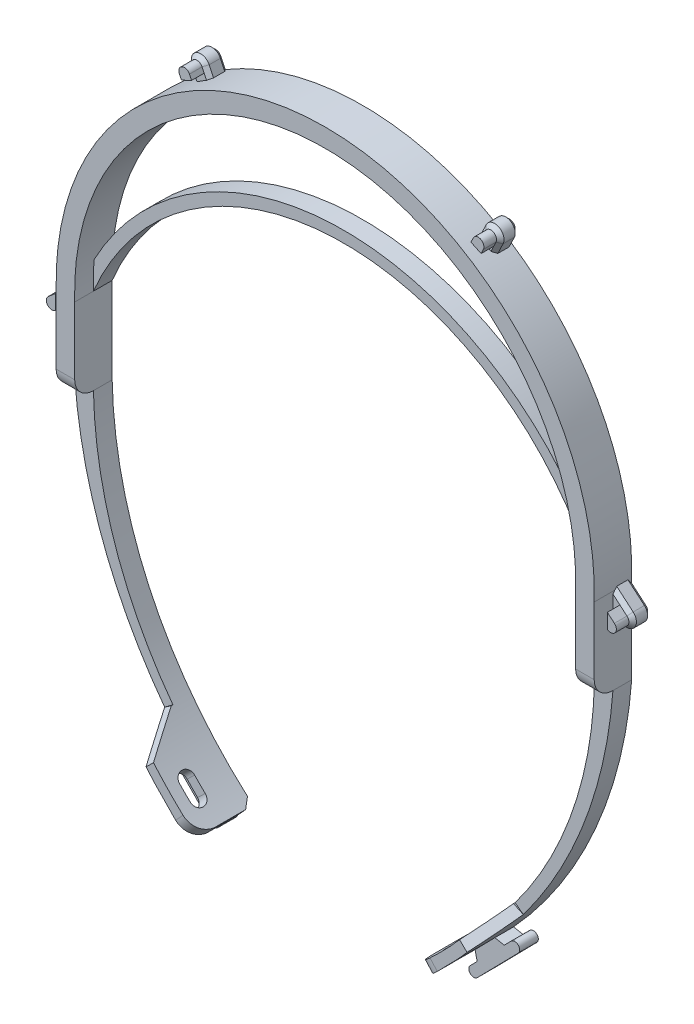
SolidWorks part; units mm, degrees
ref_plane "Plan de face" through (0, 0, 0) normal (0, 0, 1) x (1, 0, 0)
ref_plane "Plan de dessus" through (0, 0, 0) normal (0, 1, 0) x (1, 0, 0)
ref_plane "Plan de droite" through (0, 0, 0) normal (1, 0, 0) x (0, 0, -1)
sketch "Model" plane through (0, 0, 0) normal (0, 0, 1) x (1, 0, 0)
  line L0 (55.1962, 55.166) -> (59.6015, 49.7259) construction
  line L1 (19.4014, 75.8321) -> (26.163, 74.0203) construction
  line L2 (44.8062, 64.5211) -> (50.2463, 60.1158) construction
  line L3 (-41.0201, -88.1014) -> (-30.0985, -99.2461) construction
  line L4 (-41.1662, -87.9237) -> (-41.0201, -88.1014) construction
  line L5 (-41.2792, -87.7232) -> (-41.1662, -87.9237) construction
  line L6 (-40.8235, -86.0886) -> (-41.0012, -86.2347) construction
  line L7 (-40.6231, -85.9756) -> (-40.8235, -86.0886) construction
  line L8 (26.163, 74.0203) -> (32.6982, 71.5117) construction
  line L9 (66.592, 37.6179) -> (69.1007, 31.0827) construction
  line L10 (50.2463, 60.1158) -> (55.1962, 55.166) construction
  line L11 (59.6015, 49.7259) -> (63.414, 43.8551) construction
  line L12 (38.9354, 68.3337) -> (44.8062, 64.5211) construction
  line L13 (-41.3934, -87.2793) -> (-41.3557, -87.5062) construction
  line L14 (-50.2711, -66.4437) -> (-46.1557, -73.0626) construction
  line L15 (-53.9563, -59.576) -> (-50.2711, -66.4437) construction
  line L16 (-57.1961, -52.4873) -> (-53.9563, -59.576) construction
  line L17 (-62.2889, -37.7632) -> (-59.9774, -45.2065) construction
  line L18 (-29.7256, -99.5128) -> (-29.9237, -99.3957) construction
  line L19 (32.6982, 71.5117) -> (38.9354, 68.3337) construction
  line L20 (-30.0607, -95.5127) -> (-29.5051, -92.9641) construction
  line L21 (12.4875, 76.9271) -> (19.4014, 75.8321) construction
  line L22 (5.4969, 77.2935) -> (12.4875, 76.9271) construction
  line L23 (-64.1213, -30.1877) -> (-62.2889, -37.7632) construction
  line L24 (69.1007, 31.0827) -> (70.9124, 24.3211) construction
  line L25 (63.414, 43.8551) -> (66.592, 37.6179) construction
  line L26 (-61.3805, 8.2198) -> (-80.0464, 8.2198) construction
  line L27 (-28.0668, -97.576) -> (-27.9538, -97.7764) construction
  line L28 (-34.5258, -83.7152) -> (-34.4191, -83.8276) construction
  line L29 (-39.1345, -86.2536) -> (-39.3093, -86.1039) construction
  line L30 (-29.284, -99.6359) -> (-29.5102, -99.5937) construction
  line L31 (-30.0607, -95.5127) -> (-28.2129, -97.3983) construction
  line L32 (-37.2868, -88.1391) -> (-34.682, -87.6262) construction
  line L33 (-37.2868, -88.1391) -> (-39.1345, -86.2536) construction
  line L34 (-39.3093, -86.1039) -> (-39.5074, -85.9869) construction
  line L35 (-39.5074, -85.9869) -> (-39.7228, -85.906) construction
  line L36 (-39.7228, -85.906) -> (-39.949, -85.8638) construction
  line L37 (-39.949, -85.8638) -> (-40.179, -85.8614) construction
  line L38 (-40.179, -85.8614) -> (-40.406, -85.8991) construction
  line L39 (-40.406, -85.8991) -> (-40.6231, -85.9756) construction
  line L40 (-41.0012, -86.2347) -> (-41.1509, -86.4095) construction
  line L41 (-41.1509, -86.4095) -> (-41.2679, -86.6076) construction
  line L42 (-41.2679, -86.6076) -> (-41.3488, -86.823) construction
  line L43 (-41.3488, -86.823) -> (-41.391, -87.0492) construction
  line L44 (-41.391, -87.0492) -> (-41.3934, -87.2793) construction
  line L45 (-41.3557, -87.5062) -> (-41.2792, -87.7232) construction
  line L46 (-29.9237, -99.3957) -> (-30.0985, -99.2461) construction
  line L47 (-29.5102, -99.5937) -> (-29.7256, -99.5128) construction
  line L48 (-29.0539, -99.6382) -> (-29.284, -99.6359) construction
  line L49 (-28.827, -99.6006) -> (-29.0539, -99.6382) construction
  line L50 (-28.61, -99.5241) -> (-28.827, -99.6006) construction
  line L51 (-28.4095, -99.4111) -> (-28.61, -99.5241) construction
  line L52 (-28.2318, -99.2649) -> (-28.4095, -99.4111) construction
  line L53 (-28.0821, -99.0902) -> (-28.2318, -99.2649) construction
  line L54 (-27.9651, -98.8921) -> (-28.0821, -99.0902) construction
  line L55 (-27.8842, -98.6767) -> (-27.9651, -98.8921) construction
  line L56 (-27.842, -98.4505) -> (-27.8842, -98.6767) construction
  line L57 (-27.8396, -98.2204) -> (-27.842, -98.4505) construction
  line L58 (-27.8773, -97.9934) -> (-27.8396, -98.2204) construction
  line L59 (-27.9538, -97.7764) -> (-27.8773, -97.9934) construction
  line L60 (-28.2129, -97.3983) -> (-28.0668, -97.576) construction
  line L61 (-24.2049, -93.8762) -> (-24.5023, -93.6043) construction
  line L62 (-25.2785, -92.8945) -> (-25.7431, -92.4697) construction
  line L63 (-26.7824, -91.5194) -> (-27.338, -91.0114) construction
  line L64 (-24.5023, -93.6043) -> (-24.8624, -93.275) construction
  line L65 (-26.2475, -92.0085) -> (-26.7824, -91.5194) construction
  line L66 (-25.7431, -92.4697) -> (-26.2475, -92.0085) construction
  line L67 (-24.8624, -93.275) -> (-25.2785, -92.8945) construction
  line L68 (-61.3805, -14.6397) -> (-60.9807, -22.1952) construction
  line L69 (-41.6267, -79.4056) -> (-41.828, -79.1237) construction
  line L70 (-36.7026, -85.447) -> (-41.6267, -79.4056) construction
  line L71 (-51.1296, -58.5251) -> (-47.6574, -65.2474) construction
  line L72 (-58.5894, -37.1277) -> (-56.6093, -44.4301) construction
  line L73 (-46.1557, -73.0626) -> (-43.1854, -77.2225) construction
  line L74 (-43.7192, -71.7078) -> (-40.9267, -75.6351) construction
  line L75 (-47.6574, -65.2474) -> (-43.7192, -71.7078) construction
  line L76 (-54.1186, -51.5744) -> (-51.1296, -58.5251) construction
  line L77 (-56.6093, -44.4301) -> (-54.1186, -51.5744) construction
  line L78 (-60.0489, -29.7037) -> (-58.5894, -37.1277) construction
  line L79 (-60.9807, -22.1952) -> (-60.0489, -29.7037) construction
  line L80 (-66.3205, -14.7637) -> (-61.3805, -14.6397) construction
  line L81 (-66.3205, -14.7637) -> (-65.467, -22.5108) construction
  line L82 (-65.467, -22.5108) -> (-64.1213, -30.1877) construction
  line L83 (-59.9774, -45.2065) -> (-57.1961, -52.4873) construction
  line L84 (-23.7374, -94.3037) -> (-25.7505, -96.528) construction
  line L85 (-52.6046, 52.6299) -> (-56.6988, 46.3253) construction
  line L86 (-66.3205, 10.4166) -> (-66.3205, 8.871) construction
  line L87 (-47.8738, 58.4719) -> (-52.6046, 52.6299) construction
  line L88 (-36.7163, 68.5182) -> (-42.5583, 63.7874) construction
  line L89 (-65.9271, 17.9236) -> (-66.3205, 10.4166) construction
  line L90 (-64.7511, 25.3483) -> (-65.9271, 17.9236) construction
  line L91 (-62.8055, 32.6094) -> (-64.7511, 25.3483) construction
  line L92 (-60.1116, 39.6274) -> (-62.8055, 32.6094) construction
  line L93 (-56.6988, 46.3253) -> (-60.1116, 39.6274) construction
  line L94 (-42.5583, 63.7874) -> (-47.8738, 58.4719) construction
  line L95 (-34.5787, 69.9063) -> (-36.7163, 68.5182) construction
  line L96 (-23.7138, 76.0251) -> (-30.3459, 72.6459) construction
  line L97 (-16.6959, 78.7191) -> (-23.7138, 76.0251) construction
  line L98 (-9.4347, 80.6647) -> (-16.6959, 78.7191) construction
  line L99 (-2.01, 81.8407) -> (-9.4347, 80.6647) construction
  line L100 (5.4969, 82.2341) -> (-2.01, 81.8407) construction
  line L101 (47.1303, 73.2493) -> (46.9839, 72.8633) construction
  line L102 (47.2245, 74.0669) -> (46.2231, 74.0574) construction
  line L103 (47.1695, 74.4761) -> (47.2245, 74.0669) construction
  line L104 (47.1695, 74.4761) -> (46.18, 74.3153) construction
  line L105 (47.048, 74.8707) -> (47.1695, 74.4761) construction
  line L106 (47.048, 74.8707) -> (46.0928, 74.5618) construction
  line L107 (46.18, 74.3153) -> (46.0928, 74.5618) construction
  line L108 (43.6086, 76.1757) -> (44.1059, 75.3052) construction
  line L109 (43.6086, 76.1757) -> (43.9918, 76.3294) construction
  line L110 (46.3254, 75.8629) -> (45.9871, 76.0997) construction
  line L111 (47.2112, 73.6542) -> (46.2207, 73.796) construction
  line L112 (46.173, 73.5389) -> (46.2207, 73.796) construction
  line L113 (42.6795, 75.3736) -> (42.9434, 75.6912) construction
  line L114 (42.6795, 75.3736) -> (43.5067, 74.8115) construction
  line L115 (44.8718, 75.4332) -> (44.6104, 75.4355) construction
  line L116 (43.6086, 76.1757) -> (43.2559, 75.961) construction
  line L117 (46.2231, 74.0574) -> (46.18, 74.3153) construction
  line L118 (47.1303, 73.2493) -> (47.2112, 73.6542) construction
  line L119 (42.7444, 73.2671) -> (42.1891, 72.1036) construction
  line L120 (44.7267, 70.4557) -> (45.4518, 71.9749) construction
  line L121 (42.7444, 73.2671) -> (45.4518, 71.9749) construction
  line L122 (46.6201, 75.5737) -> (46.3254, 75.8629) construction
  line L123 (42.4715, 75.017) -> (42.6795, 75.3736) construction
  line L124 (46.9839, 72.8633) -> (45.5726, 69.9064) construction
  line L125 (47.1303, 73.2493) -> (46.173, 73.5389) construction
  line L126 (46.0814, 73.294) -> (46.173, 73.5389) construction
  line L127 (46.8632, 75.2399) -> (45.9641, 74.7894) construction
  line L128 (46.6201, 75.5737) -> (46.8632, 75.2399) construction
  line L129 (43.9918, 76.3294) -> (44.3952, 76.4179) construction
  line L130 (45.3738, 75.2938) -> (45.1289, 75.3855) construction
  line L131 (44.3952, 76.4179) -> (44.6104, 75.4355) construction
  line L132 (44.3952, 76.4179) -> (44.8075, 76.4389) construction
  line L133 (45.4518, 71.9749) -> (46.0814, 73.294) construction
  line L134 (46.0928, 74.5618) -> (45.9641, 74.7894) construction
  line L135 (42.4715, 75.017) -> (41.3398, 72.6459) construction
  line L136 (43.374, 74.5862) -> (42.7444, 73.2671) construction
  line L137 (44.8075, 76.4389) -> (45.2177, 76.3916) construction
  line L138 (43.8784, 75.1765) -> (43.6766, 75.0103) construction
  line L139 (43.2559, 75.961) -> (43.8784, 75.1765) construction
  line L140 (45.9871, 76.0997) -> (45.6145, 76.2775) construction
  line L141 (43.5067, 74.8115) -> (43.374, 74.5862) construction
  line L142 (45.1289, 75.3855) -> (44.8718, 75.4332) construction
  line L143 (45.599, 75.1611) -> (45.3738, 75.2938) construction
  line L144 (45.6145, 76.2775) -> (45.2177, 76.3916) construction
  line L145 (47.2245, 74.0669) -> (47.2112, 73.6542) construction
  line L146 (43.2559, 75.961) -> (42.9434, 75.6912) construction
  line L147 (43.9918, 76.3294) -> (44.3525, 75.3924) construction
  line L148 (45.9641, 74.7894) -> (45.7978, 74.9912) construction
  line L149 (44.6104, 75.4355) -> (44.3525, 75.3924) construction
  line L150 (47.048, 74.8707) -> (46.8632, 75.2399) construction
  line L151 (82.107, 1.7357) -> (82.3207, 2.0891) construction
  line L152 (43.6766, 75.0103) -> (43.5067, 74.8115) construction
  line L153 (42.9434, 75.6912) -> (43.6766, 75.0103) construction
  line L154 (78.7882, 1.0623) -> (79.158, 0.8786) construction
  line L155 (82.5804, 3.2887) -> (82.532, 3.6987) construction
  line L156 (79.9624, 0.7045) -> (80.375, 0.7189) construction
  line L157 (82.4733, 2.4727) -> (82.5606, 2.8763) construction
  line L158 (81.0333, 2.0419) -> (81.2202, 2.2248) construction
  line L159 (82.5606, 2.8763) -> (82.5804, 3.2887) construction
  line L160 (44.1059, 75.3052) -> (43.8784, 75.1765) construction
  line L161 (82.3207, 2.0891) -> (82.4733, 2.4727) construction
  line L162 (18.7844, 55.0349) -> (4.2564, 56.0412) construction
  line L163 (78.4538, 1.3045) -> (78.7882, 1.0623) construction
  line L164 (82.0001, 4.8049) -> (81.71, 5.0988) construction
  line L165 (67.4479, 25.4789) -> (57.6392, 36.2429) construction
  line L166 (82.4167, 4.0952) -> (82.2378, 4.4674) construction
  line L167 (80.375, 0.7189) -> (80.7797, 0.801) construction
  line L168 (57.6392, 36.2429) -> (45.9684, 44.9531) construction
  line L169 (32.8584, 51.2937) -> (18.7844, 55.0349) construction
  line L170 (82.2378, 4.4674) -> (82.0001, 4.8049) construction
  line L171 (82.0001, 4.8049) -> (81.2416, 4.153) construction
  line L172 (-22.8532, 47.0122) -> (-9.545, 51.3072) construction
  line L173 (4.2564, 56.0412) -> (-10.1991, 54.276) construction
  line L174 (81.5213, 1.1576) -> (81.8381, 1.4224) construction
  line L175 (-24.058, 49.8033) -> (-36.8182, 42.7853) construction
  line L176 (45.9684, 44.9531) -> (32.8584, 51.2937) construction
  line L177 (81.8381, 1.4224) -> (82.107, 1.7357) construction
  line L178 (80.7797, 0.801) -> (81.1653, 0.9486) construction
  line L179 (45.7978, 74.9912) -> (45.599, 75.1611) construction
  line L180 (82.5804, 3.2887) -> (81.5818, 3.185) construction
  line L181 (-10.1991, 54.276) -> (-24.058, 49.8033) construction
  line L182 (79.553, 0.7582) -> (79.9624, 0.7045) construction
  line L183 (-48.0172, 33.4762) -> (-57.249, 22.2136) construction
  line L184 (82.532, 3.6987) -> (82.4167, 4.0952) construction
  line L185 (-57.8611, 21.3639) -> (-58.0684, 21.3148) construction
  line L186 (-58.6266, 21.769) -> (-59.9185, 24.3211) construction
  line L187 (69.0499, 22.856) -> (67.4479, 25.4789) construction
  line L188 (65.0162, 23.6545) -> (72.3594, 8.2198) construction
  line L189 (55.5973, 33.9908) -> (65.0162, 23.6545) construction
  line L190 (44.3903, 42.3548) -> (55.5973, 33.9908) construction
  line L191 (31.8013, 48.4434) -> (44.3903, 42.3548) construction
  line L192 (18.2866, 52.036) -> (31.8013, 48.4434) construction
  line L193 (4.336, 53.0022) -> (18.2866, 52.036) construction
  line L194 (-9.545, 51.3072) -> (4.336, 53.0022) construction
  line L195 (-35.1063, 40.2731) -> (-22.8532, 47.0122) construction
  line L196 (-45.8602, 31.334) -> (-35.1063, 40.2731) construction
  line L197 (-54.7252, 20.5189) -> (-45.8602, 31.334) construction
  line L198 (-61.3805, 8.2198) -> (-54.7252, 20.5189) construction
  line L199 (-57.249, 22.2136) -> (-57.4979, 21.7536) construction
  line L200 (-36.8182, 42.7853) -> (-48.0172, 33.4762) construction
  line L201 (70.0355, 22.6643) -> (69.8462, 22.5116) construction
  line L202 (-57.4979, 21.7536) -> (-57.6665, 21.5136) construction
  line L203 (-57.6665, 21.5136) -> (-57.8611, 21.3639) construction
  line L204 (-58.0684, 21.3148) -> (-58.2742, 21.3696) construction
  line L205 (-58.2742, 21.3696) -> (-58.4646, 21.5245) construction
  line L206 (-58.4646, 21.5245) -> (-58.6266, 21.769) construction
  line L207 (69.6388, 22.4538) -> (69.4275, 22.4949) construction
  line L208 (70.1939, 22.9016) -> (70.9124, 24.3211) construction
  line L209 (81.1653, 0.9486) -> (81.5213, 1.1576) construction
  line L210 (79.158, 0.8786) -> (79.553, 0.7582) construction
  line L211 (69.2267, 22.6321) -> (69.0499, 22.856) construction
  line L212 (69.4275, 22.4949) -> (69.2267, 22.6321) construction
  line L213 (70.1939, 22.9016) -> (70.0355, 22.6643) construction
  line L214 (69.8462, 22.5116) -> (69.6388, 22.4538) construction
  line L215 (-68.9685, 0.7045) -> (-69.3811, 0.7189) construction
  line L216 (-68.1641, 0.8786) -> (-68.5591, 0.7582) construction
  line L217 (-70.3787, 2.4373) -> (-70.4918, 2.673) construction
  line L218 (-68.1641, 0.8786) -> (-68.5594, 1.7979) construction
  line L219 (-69.3811, 0.7189) -> (-69.7858, 0.801) construction
  line L220 (-69.7858, 0.801) -> (-70.1714, 0.9486) construction
  line L221 (-71.4228, 4.0952) -> (-70.5032, 3.699) construction
  line L222 (-69.7858, 0.801) -> (-69.5853, 1.7865) construction
  line L223 (-71.1131, 1.7357) -> (-71.3268, 2.0891) construction
  line L224 (-68.5591, 0.7582) -> (-68.8112, 1.7274) construction
  line L225 (-33.8136, 76.4388) -> (-34.2238, 76.3916) construction
  line L226 (-67.7943, 1.0623) -> (-68.1641, 0.8786) construction
  line L227 (-35.8693, 75.2399) -> (-34.9702, 74.7894) construction
  line L228 (-71.5667, 2.8763) -> (-70.5623, 2.9248) construction
  line L229 (-67.4599, 1.3044) -> (-67.7943, 1.0623) construction
  line L230 (-71.0062, 4.8049) -> (-70.7161, 5.0988) construction
  line L231 (-36.2306, 74.0669) -> (-36.2173, 73.6542) construction
  line L232 (-70.5274, 1.1576) -> (-70.8442, 1.4224) construction
  line L233 (-34.2238, 76.3916) -> (-34.6206, 76.2775) construction
  line L234 (-69.3811, 0.7189) -> (-69.332, 1.7216) construction
  line L235 (-71.5381, 3.6987) -> (-71.4228, 4.0952) construction
  line L236 (-32.9979, 76.3294) -> (-33.4013, 76.4179) construction
  line L237 (-71.5381, 3.6987) -> (-70.568, 3.4457) construction
  line L238 (-71.5865, 3.2887) -> (-70.5879, 3.185) construction
  line L239 (-71.5667, 2.8763) -> (-71.5865, 3.2887) construction
  line L240 (-70.8442, 1.4224) -> (-71.1131, 1.7357) construction
  line L241 (-68.9685, 0.7045) -> (-69.0714, 1.7017) construction
  line L242 (-71.4794, 2.4727) -> (-71.5667, 2.8763) construction
  line L243 (-71.3268, 2.0891) -> (-71.4794, 2.4727) construction
  line L244 (-35.6262, 75.5737) -> (-35.8693, 75.2399) construction
  line L245 (-36.0541, 74.8707) -> (-36.1756, 74.4761) construction
  line L246 (-34.9932, 76.0997) -> (-35.3315, 75.8629) construction
  line L247 (-33.4013, 76.4179) -> (-33.8136, 76.4388) construction
  line L248 (-32.6147, 76.1757) -> (-32.9979, 76.3294) construction
  line L249 (-36.1756, 74.4761) -> (-36.2306, 74.0669) construction
  line L250 (-36.1364, 73.2493) -> (-35.99, 72.8633) construction
  line L251 (-36.2306, 74.0669) -> (-35.2292, 74.0574) construction
  line L252 (-34.6206, 76.2775) -> (-34.9932, 76.0997) construction
  line L253 (-68.5591, 0.7582) -> (-68.9685, 0.7045) construction
  line L254 (80.326, 1.7216) -> (80.5793, 1.7865) construction
  line L255 (81.3726, 2.4373) -> (81.4857, 2.673) construction
  line L256 (81.3892, 3.9372) -> (81.2416, 4.153) construction
  line L257 (81.4971, 3.699) -> (81.3892, 3.9372) construction
  line L258 (80.5793, 1.7865) -> (80.8175, 1.8943) construction
  line L259 (79.8051, 1.7274) -> (80.0653, 1.7017) construction
  line L260 (81.5562, 2.9248) -> (81.5818, 3.185) construction
  line L261 (79.3175, 1.911) -> (79.5533, 1.7979) construction
  line L262 (80.0653, 1.7017) -> (80.326, 1.7216) construction
  line L263 (81.5619, 3.4457) -> (81.4971, 3.699) construction
  line L264 (79.1866, 1.9933) -> (79.3175, 1.911) construction
  line L265 (79.5533, 1.7979) -> (79.8051, 1.7274) construction
  line L266 (80.8175, 1.8943) -> (81.0333, 2.0419) construction
  line L267 (81.2202, 2.2248) -> (81.3726, 2.4373) construction
  line L268 (81.4857, 2.673) -> (81.5562, 2.9248) construction
  line L269 (81.5818, 3.185) -> (81.5619, 3.4457) construction
  line L270 (81.2416, 4.153) -> (81.0588, 4.3399) construction
  line L271 (81.0588, 4.3399) -> (79.1866, 5.9466) construction
  line L272 (79.1866, 5.9466) -> (79.1866, 1.9933) construction
  line L273 (-1.4936, 76.9271) -> (-8.4075, 75.8321) construction
  line L274 (5.4969, 77.2935) -> (-1.4936, 76.9271) construction
  line L275 (79.9624, 0.7045) -> (80.0653, 1.7017) construction
  line L276 (82.532, 3.6987) -> (81.5619, 3.4457) construction
  line L277 (79.553, 0.7582) -> (79.8051, 1.7274) construction
  line L278 (82.5606, 2.8763) -> (81.5562, 2.9248) construction
  line L279 (79.158, 0.8786) -> (79.5533, 1.7979) construction
  line L280 (82.4167, 4.0952) -> (81.4971, 3.699) construction
  line L281 (80.375, 0.7189) -> (80.326, 1.7216) construction
  line L282 (79.1866, 5.9466) -> (77.3144, 7.5532) construction
  line L283 (81.71, 5.0988) -> (77.3144, 8.871) construction
  line L284 (-33.6165, 75.4355) -> (-33.3586, 75.3924) construction
  line L285 (-35.0875, 73.294) -> (-35.1791, 73.5389) construction
  line L286 (-31.4776, 75.0169) -> (-31.6856, 75.3736) construction
  line L287 (-35.3315, 75.8629) -> (-35.6262, 75.5737) construction
  line L288 (-35.2268, 73.796) -> (-35.2292, 74.0574) construction
  line L289 (-32.262, 75.961) -> (-32.8845, 75.1765) construction
  line L290 (-34.8039, 74.9912) -> (-34.6051, 75.1611) construction
  line L291 (-35.2292, 74.0574) -> (-35.1861, 74.3153) construction
  line L292 (-35.99, 72.8633) -> (-34.5787, 69.9063) construction
  line L293 (-31.7505, 73.2671) -> (-34.4579, 71.9749) construction
  line L294 (-32.6147, 76.1757) -> (-33.112, 75.3052) construction
  line L295 (-32.5128, 74.8115) -> (-32.3801, 74.5862) construction
  line L296 (-34.3799, 75.2938) -> (-34.135, 75.3855) construction
  line L297 (-31.9495, 75.6912) -> (-32.262, 75.961) construction
  line L298 (-31.9495, 75.6912) -> (-32.6827, 75.0102) construction
  line L299 (-36.2173, 73.6542) -> (-35.2268, 73.796) construction
  line L300 (-34.4579, 71.9749) -> (-35.0875, 73.294) construction
  line L301 (-33.7328, 70.4557) -> (-34.4579, 71.9749) construction
  line L302 (-32.262, 75.961) -> (-32.6147, 76.1757) construction
  line L303 (-34.135, 75.3855) -> (-33.8779, 75.4332) construction
  line L304 (-34.6051, 75.1611) -> (-34.3799, 75.2938) construction
  line L305 (-34.9702, 74.7894) -> (-34.8039, 74.9912) construction
  line L306 (-31.6856, 75.3736) -> (-32.5128, 74.8115) construction
  line L307 (-33.3586, 75.3924) -> (-33.112, 75.3052) construction
  line L308 (-35.8693, 75.2399) -> (-36.0541, 74.8707) construction
  line L309 (-36.0541, 74.8707) -> (-35.0989, 74.5618) construction
  line L310 (-33.8779, 75.4332) -> (-33.6165, 75.4355) construction
  line L311 (-33.112, 75.3052) -> (-32.8845, 75.1765) construction
  line L312 (-32.3801, 74.5862) -> (-31.7505, 73.2671) construction
  line L313 (-32.6827, 75.0102) -> (-32.5128, 74.8115) construction
  line L314 (-32.8845, 75.1765) -> (-32.6827, 75.0102) construction
  line L315 (-35.0989, 74.5618) -> (-34.9702, 74.7894) construction
  line L316 (-35.1861, 74.3153) -> (-35.0989, 74.5618) construction
  line L317 (-35.1791, 73.5389) -> (-35.2268, 73.796) construction
  line L318 (-31.7505, 73.2671) -> (-31.1952, 72.1036) construction
  line L319 (-30.3459, 72.6459) -> (-31.4776, 75.0169) construction
  line L320 (-36.2173, 73.6542) -> (-36.1364, 73.2493) construction
  line L321 (-36.1364, 73.2493) -> (-35.1791, 73.5389) construction
  line L322 (-36.1756, 74.4761) -> (-35.1861, 74.3153) construction
  line L323 (-31.6856, 75.3736) -> (-31.9495, 75.6912) construction
  line L324 (-32.9979, 76.3294) -> (-33.3586, 75.3924) construction
  line L325 (-33.4013, 76.4179) -> (-33.6165, 75.4355) construction
  line L326 (44.3525, 75.3924) -> (44.1059, 75.3052) construction
  line L327 (46.2207, 73.796) -> (46.2231, 74.0574) construction
  line L328 (-70.5623, 2.9248) -> (-70.5879, 3.185) construction
  line L329 (-71.2439, 4.4674) -> (-70.3953, 3.9372) construction
  line L330 (-71.0062, 4.8049) -> (-70.2477, 4.153) construction
  line L331 (-71.2439, 4.4674) -> (-71.0062, 4.8049) construction
  line L332 (-71.5865, 3.2887) -> (-71.5381, 3.6987) construction
  line L333 (-70.2263, 2.2247) -> (-70.3787, 2.4373) construction
  line L334 (-70.4918, 2.673) -> (-70.5623, 2.9248) construction
  line L335 (-71.4228, 4.0952) -> (-71.2439, 4.4674) construction
  line L336 (-68.1927, 1.9933) -> (-68.3236, 1.911) construction
  line L337 (-68.1927, 5.9466) -> (-68.1927, 1.9933) construction
  line L338 (-70.568, 3.4457) -> (-70.5032, 3.699) construction
  line L339 (-66.3205, 2.2822) -> (-67.4599, 1.3044) construction
  line L340 (-70.3953, 3.9372) -> (-70.2477, 4.153) construction
  line L341 (-68.1927, 5.9466) -> (-66.3205, 7.5532) construction
  line L342 (-70.7161, 5.0988) -> (-66.3205, 8.871) construction
  line L343 (-70.5032, 3.699) -> (-70.3953, 3.9372) construction
  line L344 (-70.5879, 3.185) -> (-70.568, 3.4457) construction
  line L345 (-27.338, -91.0114) -> (-29.3008, -93.158) construction
  line L346 (-26.8674, -95.4678) -> (-26.5134, -95.8038) construction
  line L347 (-24.2049, -93.8762) -> (-26.2211, -96.0813) construction
  line L348 (-24.8624, -93.275) -> (-26.8674, -95.4678) construction
  line L349 (-24.5023, -93.6043) -> (-26.5134, -95.8038) construction
  line L350 (-26.5134, -95.8038) -> (-26.2211, -96.0813) construction
  line L351 (-23.9757, -94.0858) -> (-25.9958, -96.2951) construction
  line L352 (-26.7824, -91.5194) -> (-28.7547, -93.6764) construction
  line L353 (-25.7431, -92.4697) -> (-27.7331, -94.6461) construction
  line L354 (-25.2785, -92.8945) -> (-27.2765, -95.0795) construction
  line L355 (-23.8189, -94.2291) -> (-25.8567, -96.4271) construction
  line L356 (-28.7547, -93.6764) -> (-28.2289, -94.1755) construction
  line L357 (-39.3347, -77.874) -> (-34.5258, -83.7152) construction
  line L358 (-27.2765, -95.0795) -> (-26.8674, -95.4678) construction
  line L359 (-28.2289, -94.1755) -> (-27.7331, -94.6461) construction
  line L360 (-29.3008, -93.158) -> (-28.7547, -93.6764) construction
  line L361 (-26.2475, -92.0085) -> (-28.2289, -94.1755) construction
  line L362 (77.3144, 2.2822) -> (78.4538, 1.3045) construction
  line L363 (-59.9185, 24.3211) -> (-61.0136, 17.4071) construction
  line L364 (80.7797, 0.801) -> (80.5793, 1.7865) construction
  line L365 (82.2378, 4.4674) -> (81.3892, 3.9372) construction
  line L366 (70.9124, 24.3211) -> (72.0075, 17.4071) construction
  line L367 (-61.0136, 17.4071) -> (-61.38, 10.4166) construction
  line L368 (71.1055, 39.6274) -> (73.7994, 32.6094) construction
  line L369 (73.7994, 32.6094) -> (75.745, 25.3483) construction
  line L370 (20.4286, 80.6647) -> (27.6898, 78.7191) construction
  line L371 (75.745, 25.3483) -> (76.921, 17.9236) construction
  line L372 (47.7102, 68.5182) -> (53.5522, 63.7874) construction
  line L373 (27.6898, 78.7191) -> (34.7077, 76.0251) construction
  line L374 (67.6927, 46.3253) -> (71.1055, 39.6274) construction
  line L375 (58.8677, 58.4719) -> (63.5985, 52.6299) construction
  line L376 (76.921, 17.9236) -> (77.3144, 10.4166) construction
  line L377 (53.5522, 63.7874) -> (58.8677, 58.4719) construction
  line L378 (13.0039, 81.8407) -> (20.4286, 80.6647) construction
  line L379 (-58.1068, 31.0827) -> (-59.9185, 24.3211) construction
  line L380 (72.3594, 8.2198) -> (72.3739, -11.6387) construction
  line L381 (63.5985, 52.6299) -> (67.6927, 46.3253) construction
  line L382 (5.4969, 82.2341) -> (13.0039, 81.8407) construction
  line L383 (-15.1691, 74.0203) -> (-21.7043, 71.5117) construction
  line L384 (-55.5981, 37.6179) -> (-58.1068, 31.0827) construction
  line L385 (-52.4201, 43.8551) -> (-55.5981, 37.6179) construction
  line L386 (-48.6076, 49.7259) -> (-52.4201, 43.8551) construction
  line L387 (-44.2023, 55.166) -> (-48.6076, 49.7259) construction
  line L388 (-39.2524, 60.1158) -> (-44.2023, 55.166) construction
  line L389 (-33.8123, 64.5211) -> (-39.2524, 60.1158) construction
  line L390 (-27.9415, 68.3337) -> (-33.8123, 64.5211) construction
  line L391 (-21.7043, 71.5117) -> (-27.9415, 68.3337) construction
  line L392 (-8.4075, 75.8321) -> (-15.1691, 74.0203) construction
  line L393 (-70.1714, 0.9486) -> (-70.5274, 1.1576) construction
  line L394 (-66.3205, 7.5532) -> (-66.3205, 3.6) construction
  line L395 (-69.5853, 1.7865) -> (-69.8235, 1.8943) construction
  line L396 (-68.8112, 1.7274) -> (-69.0714, 1.7017) construction
  line L397 (-69.0714, 1.7017) -> (-69.332, 1.7216) construction
  line L398 (-70.0649, 4.3399) -> (-68.1927, 5.9466) construction
  line L399 (-68.5594, 1.7979) -> (-68.8112, 1.7274) construction
  line L400 (-70.2477, 4.153) -> (-70.0649, 4.3399) construction
  line L401 (-70.0393, 2.0419) -> (-70.2263, 2.2247) construction
  line L402 (-69.8235, 1.8943) -> (-70.0393, 2.0419) construction
  line L403 (-69.332, 1.7216) -> (-69.5853, 1.7865) construction
  line L404 (-68.3236, 1.911) -> (-68.5594, 1.7979) construction
  line L405 (71.0296, -45.2454) -> (68.24, -52.523) construction
  line L406 (34.7266, -94.3079) -> (36.7444, -96.528) construction
  line L407 (52.64, -79.4236) -> (53.1192, -78.754) construction
  line L408 (67.6623, -44.4651) -> (65.1635, -51.6066) construction
  line L409 (72.3739, -14.6397) -> (72.059, -22.2352) construction
  line L410 (76.545, -22.556) -> (75.1905, -30.2313) construction
  line L411 (47.709, -85.4594) -> (52.64, -79.4236) construction
  line L412 (58.6868, -65.2722) -> (54.7412, -71.7281) construction
  line L413 (36.7415, -92.4696) -> (37.2464, -92.009) construction
  line L414 (37.2464, -92.009) -> (37.7819, -91.5205) construction
  line L415 (75.1905, -30.2313) -> (73.3496, -37.8047) construction
  line L416 (34.7266, -94.3079) -> (34.8153, -94.2268) construction
  line L417 (34.8153, -94.2268) -> (34.9723, -94.0837) construction
  line L418 (35.2017, -93.8743) -> (35.4994, -93.6028) construction
  line L419 (35.4994, -93.6028) -> (35.8599, -93.2739) construction
  line L420 (35.8599, -93.2739) -> (36.2765, -92.8939) construction
  line L421 (37.7819, -91.5205) -> (38.3381, -91.0131) construction
  line L422 (69.6507, -37.165) -> (67.6623, -44.4651) construction
  line L423 (73.3496, -37.8047) -> (71.0296, -45.2454) construction
  line L424 (68.24, -52.523) -> (64.9921, -59.608) construction
  line L425 (57.1762, -73.0857) -> (53.799, -77.8042) construction
  line L426 (35.8599, -93.2739) -> (37.8625, -95.4691) construction
  line L427 (35.2017, -93.8743) -> (37.2155, -96.0818) construction
  line L428 (52.1699, -87.9412) -> (52.0236, -88.1188) construction
  line L429 (77.3144, -14.7637) -> (76.545, -22.556) construction
  line L430 (72.059, -22.2352) -> (71.1187, -29.7427) construction
  line L431 (35.4994, -93.6028) -> (37.5082, -95.8047) construction
  line L432 (37.8625, -95.4691) -> (37.5082, -95.8047) construction
  line L433 (34.8153, -94.2268) -> (36.8357, -96.4415) construction
  line L434 (34.9723, -94.0837) -> (36.99, -96.2954) construction
  line L435 (50.3497, -77.8893) -> (45.5342, -83.7251) construction
  line L436 (37.5082, -95.8047) -> (37.2155, -96.0818) construction
  line L437 (36.99, -96.2954) -> (36.8357, -96.4415) construction
  line L438 (36.2765, -92.8939) -> (38.272, -95.0813) construction
  line L439 (54.7412, -71.7281) -> (51.5432, -76.2149) construction
  line L440 (51.8292, -86.1058) -> (52.0068, -86.2521) construction
  line L441 (61.2992, -66.4715) -> (57.1762, -73.0857) construction
  line L442 (45.5342, -83.7251) -> (45.4273, -83.8374) construction
  line L443 (36.8357, -96.4415) -> (36.7444, -96.528) construction
  line L444 (52.0236, -88.1188) -> (41.0893, -99.251) construction
  line L445 (64.9921, -59.608) -> (61.2992, -66.4715) construction
  line L446 (52.2831, -87.7409) -> (52.1699, -87.9412) construction
  line L447 (37.7819, -91.5205) -> (39.7518, -93.6798) construction
  line L448 (40.2985, -93.162) -> (39.7518, -93.6798) construction
  line L449 (38.3381, -91.0131) -> (40.2985, -93.162) construction
  line L450 (40.5006, -99.598) -> (40.7161, -99.5173) construction
  line L451 (36.7415, -92.4696) -> (38.7291, -94.6483) construction
  line L452 (38.272, -95.0813) -> (37.8625, -95.4691) construction
  line L453 (51.629, -85.9925) -> (51.8292, -86.1058) construction
  line L454 (38.9563, -98.8946) -> (39.0731, -99.0928) construction
  line L455 (39.7518, -93.6798) -> (39.2255, -94.1783) construction
  line L456 (65.1635, -51.6066) -> (62.1667, -58.5539) construction
  line L457 (39.0731, -99.0928) -> (39.2226, -99.2678) construction
  line L458 (37.2464, -92.009) -> (39.2255, -94.1783) construction
  line L459 (52.1563, -86.427) -> (52.2731, -86.6253) construction
  line L460 (39.2255, -94.1783) -> (38.7291, -94.6483) construction
  line L461 (40.2744, -99.6399) -> (40.5006, -99.598) construction
  line L462 (71.1187, -29.7427) -> (69.6507, -37.165) construction
  line L463 (41.0558, -95.5176) -> (39.2059, -97.4011) construction
  line L464 (52.3538, -86.8408) -> (52.3957, -87.067) construction
  line L465 (50.5133, -86.0025) -> (50.7288, -85.9219) construction
  line L466 (50.7288, -85.9219) -> (50.955, -85.8799) construction
  line L467 (39.6005, -99.5273) -> (39.8174, -99.6041) construction
  line L468 (39.4002, -99.4141) -> (39.6005, -99.5273) construction
  line L469 (51.1851, -85.8779) -> (51.412, -85.9158) construction
  line L470 (52.0068, -86.2521) -> (52.1563, -86.427) construction
  line L471 (40.0443, -99.642) -> (40.2744, -99.6399) construction
  line L472 (52.2731, -86.6253) -> (52.3538, -86.8408) construction
  line L473 (40.9143, -99.4005) -> (41.0893, -99.251) construction
  line L474 (38.8316, -98.2228) -> (38.8337, -98.4529) construction
  line L475 (50.955, -85.8799) -> (51.1851, -85.8779) construction
  line L476 (38.8695, -97.9959) -> (38.8316, -98.2228) construction
  line L477 (51.412, -85.9158) -> (51.629, -85.9925) construction
  line L478 (48.2902, -88.1523) -> (50.1401, -86.2688) construction
  line L479 (52.3599, -87.524) -> (52.2831, -87.7409) construction
  line L480 (50.3151, -86.1194) -> (50.5133, -86.0025) construction
  line L481 (39.2226, -99.2678) -> (39.4002, -99.4141) construction
  line L482 (38.8337, -98.4529) -> (38.8756, -98.6791) construction
  line L483 (39.0595, -97.5787) -> (38.9463, -97.7789) construction
  line L484 (38.9463, -97.7789) -> (38.8695, -97.9959) construction
  line L485 (48.2902, -88.1523) -> (45.686, -87.6363) construction
  line L486 (50.1401, -86.2688) -> (50.3151, -86.1194) construction
  line L487 (39.2059, -97.4011) -> (39.0595, -97.5787) construction
  line L488 (38.8756, -98.6791) -> (38.9563, -98.8946) construction
  line L489 (41.0558, -95.5176) -> (40.503, -92.9684) construction
  line L490 (52.3957, -87.067) -> (52.3978, -87.2971) construction
  line L491 (39.8174, -99.6041) -> (40.0443, -99.642) construction
  line L492 (52.3978, -87.2971) -> (52.3599, -87.524) construction
  line L493 (62.1667, -58.5539) -> (58.6868, -65.2722) construction
  line L494 (40.7161, -99.5173) -> (40.9143, -99.4005) construction
  line L495 (-61.38, -13.1392) -> (-61.38, -13.7607) construction
  line L496 (-66.3205, -12.5395) -> (-66.3205, -11.7628) construction
  line L497 (-66.3205, -13.8848) -> (-61.38, -13.7607) construction
  line L498 (-66.3205, -11.7628) -> (-61.38, -11.6387) construction
  line L499 (-66.3205, -13.2633) -> (-66.3205, -12.5395) construction
  line L500 (-66.3205, -12.5395) -> (-61.38, -12.4154) construction
  line L501 (-66.3205, -13.8848) -> (-66.3205, -13.2633) construction
  line L502 (-61.38, -14.2376) -> (-61.38, -14.5374) construction
  line L503 (-61.38, -14.5374) -> (-61.3805, -14.6397) construction
  line L504 (-66.3205, -14.6615) -> (-61.38, -14.5374) construction
  line L505 (-66.3205, -14.7637) -> (-66.3205, -14.6615) construction
  line L506 (-66.3205, -13.2633) -> (-61.38, -13.1392) construction
  line L507 (-61.38, -11.6387) -> (-61.38, -12.4154) construction
  line L508 (-61.38, -12.4154) -> (-61.38, -13.1392) construction
  line L509 (-66.3205, -14.3617) -> (-66.3205, -13.8848) construction
  line L510 (-66.3205, -14.3617) -> (-61.38, -14.2376) construction
  line L511 (-66.3205, -14.6615) -> (-66.3205, -14.3617) construction
  line L512 (-61.38, -13.7607) -> (-61.38, -14.2376) construction
  line L513 (77.3144, -14.6615) -> (72.3739, -14.5374) construction
  line L514 (77.3144, -14.6615) -> (77.3144, -14.3617) construction
  line L515 (77.3144, -14.3617) -> (72.3739, -14.2376) construction
  line L516 (72.3739, -14.2376) -> (72.3739, -14.5374) construction
  line L517 (72.3739, -14.5374) -> (72.3739, -14.6397) construction
  line L518 (77.3144, -14.7637) -> (77.3144, -14.6615) construction
  line L519 (72.3739, -14.6397) -> (77.3144, -14.7637) construction
  line L520 (77.3144, -14.3617) -> (77.3144, -13.8848) construction
  line L521 (72.3739, -11.6387) -> (72.3739, -12.4154) construction
  line L522 (77.3144, -13.8848) -> (72.3739, -13.7607) construction
  line L523 (77.3144, -12.5395) -> (72.3739, -12.4154) construction
  line L524 (77.3144, -12.5395) -> (77.3144, -11.7628) construction
  line L525 (77.3144, -11.7628) -> (72.3739, -11.6387) construction
  line L526 (77.3144, -13.2633) -> (77.3144, -12.5395) construction
  line L527 (72.3739, -12.4154) -> (72.3739, -13.1392) construction
  line L528 (72.3739, -13.1392) -> (72.3739, -13.7607) construction
  line L529 (72.3739, -13.7607) -> (72.3739, -14.2376) construction
  line L530 (77.3144, -13.8848) -> (77.3144, -13.2633) construction
  line L531 (77.3144, -13.2633) -> (72.3739, -13.1392) construction
  line L532 (-39.573, -77.5389) -> (-39.3347, -77.874) construction
  line L533 (-40.1985, -76.6592) -> (-42.4552, -78.2453) construction
  line L534 (-42.2128, -78.5848) -> (-42.4552, -78.2453) construction
  line L535 (-39.9567, -76.9992) -> (-42.2128, -78.5848) construction
  line L536 (-40.1985, -76.6592) -> (-39.9567, -76.9992) construction
  line L537 (-40.7006, -75.9531) -> (-40.4522, -76.3024) construction
  line L538 (-39.7434, -77.2993) -> (-41.9988, -78.8844) construction
  line L539 (-41.828, -79.1237) -> (-41.9988, -78.8844) construction
  line L540 (-39.573, -77.5389) -> (-41.828, -79.1237) construction
  line L541 (-39.7434, -77.2993) -> (-39.573, -77.5389) construction
  line L542 (-40.9267, -75.6351) -> (-40.7006, -75.9531) construction
  line L543 (-41.9988, -78.8844) -> (-42.2128, -78.5848) construction
  line L544 (-39.9567, -76.9992) -> (-39.7434, -77.2993) construction
  line L545 (-40.4522, -76.3024) -> (-40.1985, -76.6592) construction
  line L546 (-42.4552, -78.2453) -> (-42.7096, -77.8889) construction
  line L547 (-43.1854, -77.2225) -> (-40.9267, -75.6351) construction
  line L548 (-42.9587, -77.5401) -> (-43.1854, -77.2225) construction
  line L549 (-40.4522, -76.3024) -> (-42.7096, -77.8889) construction
  line L550 (-42.7096, -77.8889) -> (-42.9587, -77.5401) construction
  line L551 (-40.7006, -75.9531) -> (-42.9587, -77.5401) construction
  line L552 (-34.4191, -83.8276) -> (-34.3168, -83.9354) construction
  line L553 (-36.0432, -86.1582) -> (-33.742, -84.5408) construction
  line L554 (-36.3404, -85.8376) -> (-34.0435, -84.2232) construction
  line L555 (-36.3404, -85.8376) -> (-36.1902, -85.9996) construction
  line L556 (-36.1902, -85.9996) -> (-33.8911, -84.3837) construction
  line L557 (-33.8911, -84.3837) -> (-34.0435, -84.2232) construction
  line L558 (-36.4836, -85.6832) -> (-36.3404, -85.8376) construction
  line L559 (-36.1902, -85.9996) -> (-36.0432, -86.1582) construction
  line L560 (-33.742, -84.5408) -> (-33.8911, -84.3837) construction
  line L561 (-34.1887, -84.0703) -> (-34.3168, -83.9354) construction
  line L562 (-35.9093, -86.3025) -> (-33.6062, -84.6839) construction
  line L563 (-36.4836, -85.6832) -> (-34.1887, -84.0703) construction
  line L564 (-34.0435, -84.2232) -> (-34.1887, -84.0703) construction
  line L565 (-34.4191, -83.8276) -> (-36.7026, -85.447) construction
  line L566 (-36.6099, -85.547) -> (-34.3168, -83.9354) construction
  line L567 (-36.6099, -85.547) -> (-36.4836, -85.6832) construction
  line L568 (-33.742, -84.5408) -> (-33.6062, -84.6839) construction
  line L569 (-36.6099, -85.547) -> (-36.7026, -85.447) construction
  line L570 (-36.0432, -86.1582) -> (-35.9093, -86.3025) construction
  line L571 (45.4273, -83.8374) -> (45.3249, -83.945) construction
  line L572 (47.0489, -86.1699) -> (44.7494, -84.5498) construction
  line L573 (47.6162, -85.5592) -> (47.4898, -85.6954) construction
  line L574 (46.9148, -86.3141) -> (44.6134, -84.6927) construction
  line L575 (47.3465, -85.8496) -> (47.1961, -86.0115) construction
  line L576 (47.4898, -85.6954) -> (45.1966, -84.0798) construction
  line L577 (45.0513, -84.2326) -> (45.1966, -84.0798) construction
  line L578 (47.3465, -85.8496) -> (45.0513, -84.2326) construction
  line L579 (47.4898, -85.6954) -> (47.3465, -85.8496) construction
  line L580 (47.6162, -85.5592) -> (45.3249, -83.945) construction
  line L581 (45.1966, -84.0798) -> (45.3249, -83.945) construction
  line L582 (47.1961, -86.0115) -> (44.8987, -84.3929) construction
  line L583 (44.7494, -84.5498) -> (44.8987, -84.3929) construction
  line L584 (47.1961, -86.0115) -> (47.0489, -86.1699) construction
  line L585 (44.8987, -84.3929) -> (45.0513, -84.2326) construction
  line L586 (45.4273, -83.8374) -> (47.709, -85.4594) construction
  line L587 (47.6162, -85.5592) -> (47.709, -85.4594) construction
  line L588 (47.0489, -86.1699) -> (46.9148, -86.3141) construction
  line L589 (44.7494, -84.5498) -> (44.6134, -84.6927) construction
  line L590 (53.1192, -78.754) -> (53.2048, -78.6345) construction
  line L591 (50.8652, -77.1661) -> (50.3497, -77.8893) construction
  line L592 (53.799, -77.8042) -> (53.6855, -77.9629) construction
  line L593 (51.5432, -76.2149) -> (51.4299, -76.3738) construction
  line L594 (53.3119, -78.4848) -> (53.2048, -78.6345) construction
  line L595 (51.0574, -76.8965) -> (53.3119, -78.4848) construction
  line L596 (50.9506, -77.0464) -> (53.2048, -78.6345) construction
  line L597 (50.9506, -77.0464) -> (51.0574, -76.8965) construction
  line L598 (53.6855, -77.9629) -> (53.5607, -78.1371) construction
  line L599 (51.1785, -76.7266) -> (53.4333, -78.3152) construction
  line L600 (51.0574, -76.8965) -> (51.1785, -76.7266) construction
  line L601 (51.3055, -76.5483) -> (53.5607, -78.1371) construction
  line L602 (53.4333, -78.3152) -> (53.3119, -78.4848) construction
  line L603 (53.5607, -78.1371) -> (53.4333, -78.3152) construction
  line L604 (51.4299, -76.3738) -> (53.6855, -77.9629) construction
  line L605 (51.3055, -76.5483) -> (51.4299, -76.3738) construction
  line L606 (51.5432, -76.2149) -> (53.799, -77.8042) construction
  line L607 (53.1192, -78.754) -> (50.8652, -77.1661) construction
  line L608 (51.1785, -76.7266) -> (51.3055, -76.5483) construction
  line L609 (50.9506, -77.0464) -> (50.8652, -77.1661) construction
  line L610 (-66.3205, 2.2822) -> (-66.3205, -11.7628) construction
  line L611 (-29.5051, -92.9641) -> (-29.3008, -93.158) construction
  line L612 (72.0075, 17.4071) -> (72.3594, 8.2198) construction
  line L613 (-61.38, 10.4166) -> (-61.3805, 8.2198) construction
  line L614 (-61.3805, 8.2198) -> (-61.38, -11.6387) construction
  line L615 (34.7077, 76.0251) -> (41.3398, 72.6459) construction
  line L616 (41.3398, 72.6459) -> (41.4057, 72.6124) construction
  line L617 (-30.3459, 72.6459) -> (-30.4118, 72.6124) construction
  line L618 (40.503, -92.9684) -> (40.2985, -93.162) construction
  line L619 (77.3144, 7.5532) -> (77.3144, 3.6) construction
  line L620 (77.3144, 3.6) -> (77.3144, 2.2822) construction
  line L621 (77.3144, 2.2822) -> (77.3144, -11.7628) construction
  line L622 (-33.7328, 70.4557) -> (-34.5787, 69.9063) construction
  line L623 (41.4057, 72.6124) -> (42.1891, 72.1036) construction
  line L624 (42.1891, 72.1036) -> (44.7267, 70.4557) construction
  line L625 (44.7267, 70.4557) -> (45.5726, 69.9064) construction
  line L626 (45.5726, 69.9064) -> (47.7102, 68.5182) construction
  line L627 (77.3144, 10.4166) -> (77.3144, 8.871) construction
  line L628 (77.3144, 8.871) -> (77.3144, 7.5532) construction
  line L629 (-30.4118, 72.6124) -> (-31.1952, 72.1036) construction
  line L630 (-31.1952, 72.1036) -> (-33.7328, 70.4557) construction
  line L631 (-66.3205, 3.6) -> (-66.3205, 2.2822) construction
  line L632 (-66.3205, 8.871) -> (-66.3205, 7.5532) construction
  line L633 (-33.6062, -84.6839) -> (-29.3165, -89.2023) construction
  line L634 (-31.4033, -91.1622) -> (-34.682, -87.6262) construction
  line L635 (-34.682, -87.6262) -> (-35.9093, -86.3025) construction
  line L636 (-23.7374, -94.3037) -> (-23.8189, -94.2291) construction
  line L637 (-29.3165, -89.2023) -> (-27.338, -91.0114) construction
  line L638 (-23.9757, -94.0858) -> (-23.8189, -94.2291) construction
  line L639 (-23.9757, -94.0858) -> (-24.2049, -93.8762) construction
  line L640 (-25.8567, -96.4271) -> (-25.7505, -96.528) construction
  line L641 (-25.8567, -96.4271) -> (-25.9958, -96.2951) construction
  line L642 (-25.9958, -96.2951) -> (-26.2211, -96.0813) construction
  line L643 (-27.7331, -94.6461) -> (-27.2765, -95.0795) construction
  line L644 (-29.5051, -92.9641) -> (-31.4033, -91.1622) construction
  line L645 (79.1866, 1.9933) -> (77.3144, 3.6) construction
  line L646 (-66.3205, 3.6) -> (-68.1927, 1.9933) construction
  line L647 (36.2765, -92.8939) -> (36.7415, -92.4696) construction
  line L648 (34.9723, -94.0837) -> (35.2017, -93.8743) construction
  line L649 (40.3186, -89.2063) -> (38.3381, -91.0131) construction
  line L650 (40.3186, -89.2063) -> (44.6134, -84.6927) construction
  line L651 (46.9148, -86.3141) -> (45.686, -87.6363) construction
  line L652 (37.2155, -96.0818) -> (36.99, -96.2954) construction
  line L653 (38.7291, -94.6483) -> (38.272, -95.0813) construction
  line L654 (40.503, -92.9684) -> (42.4033, -91.1686) construction
  line L655 (45.686, -87.6363) -> (42.4033, -91.1686) construction
  line L656 (77.3144, -14.7637) -> (-66.3205, -14.7637) construction
  line L657 (36.7444, -96.528) -> (-85.3049, 37.7568) construction
  line L658 (-61.3805, 8.2198) -> (-61.3739, -14.7637)
  line L659 (-61.3805, 8.2198) -> (72.3594, 8.2198) construction
  line L660 (72.3594, 8.2198) -> (102.2092, 8.2198) construction
  line L661 (-66.3205, 8.2121) -> (-66.3205, -14.7637)
  line L662 (72.3594, 8.2198) -> (72.3687, -14.7637)
  line L663 (72.3687, -14.7637) -> (77.3144, -14.7637)
  line L664 (77.3144, -14.7637) -> (77.3144, 8.2121)
  line L665 (-61.3739, -14.7637) -> (-66.3205, -14.7637)
  arc A0 (-61.3805, 8.2198) -> (72.3594, 8.2198) centre (5.4894, 10.2998) cw
  arc A1 (-66.3205, 8.2121) -> (77.3144, 8.2121) centre (5.497, 10.288) cw
  arc A2 (-61.3805, 8.2198) -> (72.3594, 8.2198) centre (5.4894, -19.7257) cw
  arc A4 (-61.2017, 15.611) -> (72.1805, 15.611) centre (5.4894, -19.7257) cw
  point P542 (-64.1485, 9.3766)
  point P543 (75.1274, 9.3766)
extrude "Boss.-Extru.1" add sketch "Model" along normal blind 10 contours A1 L661 L665 L658 A0 L662 L663 L664 region at (-63.1104, -3.2725, 0)
extrude "Boss.-Extru.2" add sketch "Model<3>" along normal blind 5 contours A4 A0 A2 region at (-59.9737, 11.8835, 0)
sketch "Model<3>" plane through (0, 0, 0) normal (0, 0, 1) x (1, 0, 0) same geometry as "Model"
sketch "Esquisse2" plane through (0, 0, 0) normal (0, 0, -1) x (-1, 0, 0)
  line L0 (-77.3144, 8.871) -> (-81.71, 5.0988)
  line L1 (-78.4538, 1.3045) -> (-75.8334, 3.5533)
  line L2 (-75.8334, 3.5533) -> (-75.8334, 8.871)
  line L3 (-75.8334, 8.871) -> (-77.3144, 8.871)
  line L4 (-45.5726, 69.9064) -> (-46.9839, 72.8633)
  line L5 (-42.4715, 75.017) -> (-40.7379, 71.3848)
  line L6 (-40.7379, 71.3848) -> (-45.0724, 68.8584)
  line L7 (-45.0724, 68.8584) -> (-45.5726, 69.9064)
  line L8 (34.5787, 69.9063) -> (35.99, 72.8633)
  line L9 (31.4776, 75.0169) -> (29.9545, 71.8257)
  line L10 (29.9545, 71.8257) -> (34.0742, 68.8494)
  line L11 (34.0742, 68.8494) -> (34.5787, 69.9063)
  line L12 (66.3205, 8.871) -> (70.7161, 5.0988)
  line L13 (67.4599, 1.3044) -> (65.3978, 3.0741)
  line L14 (65.3978, 3.0741) -> (65.3978, 9.6629)
  line L15 (65.3978, 9.6629) -> (66.3205, 8.871)
  arc A0 (-81.71, 5.0988) -> (-78.4538, 1.3045) centre (-80.0819, 3.2016) ccw
  arc A1 (-46.9839, 72.8633) -> (-42.4715, 75.017) centre (-44.7277, 73.9401) cw
  arc A2 (35.99, 72.8633) -> (31.4776, 75.0169) centre (33.7338, 73.9401) ccw
  arc A3 (70.7161, 5.0988) -> (67.4599, 1.3044) centre (69.088, 3.2016) cw
extrude "Boss.-Extru.3" add sketch "Esquisse2" against normal blind 5
chamfer "Chanfrein1" distance 1 angle 45 24 edges at (-68.5262, 6.9781, 0) (-66.8902, 1.7933, 0) (-70.9852, 1.5735, 0) (-68.5262, 6.9781, 5) (-66.8902, 1.7933, 5) (-70.9852, 1.5735, 5) (77.8841, 1.7934, 5) (81.9791, 1.5735, 5) (79.5201, 6.9781, 5) (77.8841, 1.7934, 0) (81.9791, 1.5735, 0) (79.5201, 6.9781, 0) (46.2807, 71.3901, 0) (45.8045, 76.1963, 0) (41.8889, 73.7963, 0) (46.2807, 71.3901, 5) (41.8889, 73.7963, 5) (45.8045, 76.1963, 5) (-30.895, 73.7963, 0) (-34.8106, 76.1963, 0) (-35.2868, 71.3901, 0) (-30.895, 73.7963, 5) (-34.8106, 76.1963, 5) (-35.2868, 71.3901, 5)
sketch "Esquisse3" plane through (0, 0, 0) normal (0, 0, -1) x (-1, 0, 0)
  line L0 (-77.3144, -14.7637) -> (-72.3687, -14.7637)
  line L1 (-72.3739, -14.6397) -> (-72.059, -22.2352) construction
  line L2 (-72.3687, -14.7637) -> (-77.3144, -14.7637) construction
  line L3 (-34.7266, -94.3079) -> (-36.7444, -96.528)
  line L4 (23.7374, -94.3037) -> (25.7505, -96.528)
  line L5 (61.3739, -14.7637) -> (66.3205, -14.7637)
  line L6 (-45.686, -87.6363) -> (-48.2902, -88.1523)
  line L7 (-48.2902, -88.1523) -> (-50.1401, -86.2688)
  line L8 (-52.0236, -88.1188) -> (-41.0893, -99.251)
  line L9 (-39.2059, -97.4011) -> (-41.0558, -95.5176)
  line L10 (-41.0558, -95.5176) -> (-40.5205, -93.0492)
  line L11 (-41.0558, -95.5176) -> (-40.503, -92.9684) construction
  line L12 (-40.5205, -93.0492) -> (-45.7906, -87.657)
  line L13 (-40.5205, -93.0492) -> (-40.2677, -91.9875)
  line L14 (-40.2677, -91.9875) -> (-44.8424, -87.3848)
  line L15 (-44.8424, -87.3848) -> (-45.686, -87.6363)
  line L16 (29.5051, -92.9641) -> (30.0607, -95.5127)
  line L17 (30.0607, -95.5127) -> (28.2129, -97.3983)
  line L18 (30.0985, -99.2461) -> (41.0201, -88.1014)
  line L19 (39.1345, -86.2536) -> (37.2868, -88.1391)
  line L20 (37.2868, -88.1391) -> (34.682, -87.6262)
  line L21 (34.682, -87.6262) -> (33.8197, -87.4563)
  line L22 (33.8197, -87.4563) -> (29.5051, -91.8592)
  line L23 (29.5051, -91.8592) -> (29.5051, -92.9641)
  arc A0 (-72.3687, -14.7637) -> (-34.7266, -94.3079) centre (33.6675, -13.2637) ccw
  arc A1 (-77.3144, -14.7637) -> (-36.7444, -96.528) centre (43.2809, -5.8736) ccw
  arc A2 (61.3739, -14.7637) -> (23.7374, -94.3037) centre (-45.6827, -12.7813) cw
  arc A3 (25.7505, -96.528) -> (66.3205, -14.7637) centre (-55.5087, -5.2614) ccw
  arc A4 (-50.1401, -86.2688) -> (-52.0236, -88.1188) centre (-51.0818, -87.1938) ccw
  arc A5 (-41.0893, -99.251) -> (-39.2059, -97.4011) centre (-40.1476, -98.326) ccw
  arc A6 (28.2129, -97.3983) -> (30.0985, -99.2461) centre (29.1557, -98.3222) ccw
  arc A7 (41.0201, -88.1014) -> (39.1345, -86.2536) centre (40.0773, -87.1775) ccw
  line M7 (-77.3144, -14.7637) -> (-72.3687, -14.7637)
extrude "Boss.-Extru.4" add sketch "Esquisse3" against normal blind 5 separate body contours A1 L6 L15 L14 L13 L3 A0 M7 | L8 A5 L9 L10 A1 L6 L7 A4 | L18 A7 L19 L20 A3 L16 L17 A6 | A3 L5 A2 L4 | L13 L14 L15 L6 L7 A4 L8 A5 L9 L10 region at (74.8416, -15.6857, 0) region at (45.1456, -92.2972, 0) region at (-34.1423, -92.2814, 0)
fillet "Congé1" radius 5 2 edges at (74.8416, -14.7637, 10) (-63.8472, -14.7637, 10)
sketch "Esquisse4" plane through (0, 0, 5) normal (0, 0, 1) x (1, 0, 0)
  line L0 (-34.7493, -87.6394) -> (-29.519, -93.0278)
  line L1 (-42.357, -78.439) -> (-40.1511, -76.7939)
  line L2 (51.1989, -76.8532) -> (53.3983, -78.5056)
  line L3 (45.7906, -87.657) -> (40.5205, -93.0492)
  line L7 (-41.0201, -88.1014) -> (-30.0985, -99.2461)
  line L8 (-28.2129, -97.3983) -> (-30.0607, -95.5127)
  line L9 (-30.0607, -95.5127) -> (-29.519, -93.0278)
  line L10 (-25.7505, -96.528) -> (-23.7374, -94.3037)
  line L11 (-61.3739, -14.7637) -> (-66.3205, -14.7637)
  line L12 (-34.7493, -87.6394) -> (-37.2868, -88.1391)
  line L13 (-37.2868, -88.1391) -> (-39.1345, -86.2536)
  line L17 (-25.7505, -96.528) -> (-23.7374, -94.3037)
  line L23 (40.5205, -93.0492) -> (41.0558, -95.5176)
  line L24 (41.0558, -95.5176) -> (39.2058, -97.4011)
  line L25 (41.0893, -99.251) -> (52.0236, -88.1188)
  line L26 (50.1401, -86.2688) -> (48.2902, -88.1523)
  line L27 (48.2902, -88.1523) -> (45.7906, -87.657)
  line L28 (77.3144, -14.7637) -> (72.3687, -14.7637)
  line L29 (34.7266, -94.3079) -> (36.7444, -96.528)
  line L36 (34.7266, -94.3079) -> (36.7444, -96.528)
  arc A5 (-30.0985, -99.2461) -> (-28.2129, -97.3983) centre (-29.1557, -98.3222) ccw
  arc A6 (-29.519, -93.0278) -> (-25.7505, -96.528) centre (55.5087, -5.2614) ccw
  arc A7 (-61.3739, -14.7637) -> (-23.7374, -94.3037) centre (45.6827, -12.7813) ccw
  arc A8 (-66.3205, -14.7637) -> (-34.7493, -87.6394) centre (55.5087, -5.2614) ccw
  arc A9 (-39.1345, -86.2536) -> (-41.0201, -88.1014) centre (-40.0773, -87.1775) ccw
  arc A11 (-29.519, -93.0278) -> (-25.7505, -96.528) centre (55.5087, -5.2614) ccw
  arc A12 (-40.1511, -76.7939) -> (-23.7374, -94.3037) centre (45.6827, -12.7813) ccw
  arc A13 (-42.357, -78.439) -> (-34.7493, -87.6394) centre (55.5087, -5.2614) ccw
  arc A15 (36.7444, -96.528) -> (40.5205, -93.0492) centre (-43.2809, -5.8736) ccw
  arc A16 (39.2058, -97.4011) -> (41.0893, -99.251) centre (40.1476, -98.326) ccw
  arc A17 (52.0236, -88.1188) -> (50.1401, -86.2688) centre (51.0818, -87.1938) ccw
  arc A18 (45.7906, -87.657) -> (77.3144, -14.7637) centre (-43.2809, -5.8736) ccw
  arc A19 (34.7266, -94.3079) -> (72.3687, -14.7637) centre (-33.6675, -13.2637) ccw
  arc A20 (36.7444, -96.528) -> (40.5205, -93.0492) centre (-43.2809, -5.8736) ccw
  arc A23 (45.7906, -87.657) -> (53.3983, -78.5056) centre (-43.2809, -5.8736) ccw
  arc A24 (34.7266, -94.3079) -> (51.1989, -76.8532) centre (-33.6675, -13.2637) ccw
  dimension "D2" = 24
  dimension "D4" = 24
  dimension "D1" = 0
  dimension "D3" = 0
extrude "Boss.-Extru.5" add sketch "Esquisse4" along normal blind 10
sketch "Esquisse5" plane through (67.2366, -65.7143, 0) normal (0.7152, -0.699, 0) x (0, 0, -1)
  line L0 (-15, -26.8202) -> (-5, -18.8202)
  line L2 (-5, -18.8202) -> (-15, -18.8202)
  line L3 (-15, -18.8202) -> (-15, -26.8202)
  dimension "D1" = 8
extrude "Enlèv. mat.-Extru.1" cut sketch "Esquisse5" against normal blind 10
sketch "Esquisse6" plane through (67.2366, -65.7143, 0) normal (0.7152, -0.699, 0) x (0, 0, -1)
  line L0 (-10, -36.6824) -> (-10, -32.6824) construction
  line L1 (-12, -36.6824) -> (-12, -32.6824)
  line L2 (-8, -36.6824) -> (-8, -32.6824)
  line L3 (-5, -38.2223) -> (-5, -30.6824) construction
  line L4 (-15, -30.6824) -> (-5, -30.6824) construction
  arc A0 (-12, -36.6824) -> (-8, -36.6824) centre (-10, -36.6824) ccw
  arc A1 (-8, -32.6824) -> (-12, -32.6824) centre (-10, -32.6824) ccw
  point P2 (-10, -34.6824)
  dimension "D3" = 2
  dimension "D1" = 5
  dimension "D2" = 4
  dimension "D4" = 2
extrude "Enlèv. mat.-Extru.2" cut sketch "Esquisse6" against normal blind 10
fillet "Congé2" radius 5 1 edges at (35.7355, -95.418, 15)
chamfer "Chanfrein2" distance 2 angle 45 1 edges at (35.7355, -95.418, 0)
chamfer "Chanfrein3" distance 2 angle 45 1 edges at (-24.744, -95.4158, 0)
fillet "Congé3" radius 5 1 edges at (-24.744, -95.4158, 15)
sketch "Esquisse7" plane through (-61.692, -59.8826, 0) normal (-0.7176, -0.6965, 0) x (0, 0, 1)
  line L0 (5, -26.7821) -> (15, -34.7821)
  line L1 (15, -38.6827) -> (15, -26.7821) construction
  line L2 (15, -34.7821) -> (15, -26.7821)
  line L3 (15, -26.7821) -> (5, -26.7821)
  dimension "D1" = 8
extrude "Enlèv. mat.-Extru.3" cut sketch "Esquisse7" against normal blind 10
sketch "Esquisse8" plane through (-61.692, -59.8826, 0) normal (-0.7176, -0.6965, 0) x (0, 0, 1)
  line L0 (10, -40.6827) -> (10, -44.6827) construction
  line L1 (12, -40.6827) -> (12, -44.6827)
  line L2 (8, -40.6827) -> (8, -44.6827)
  line L3 (15, -38.6827) -> (5, -38.6827) construction
  line L4 (5, -38.6827) -> (5, -46.1921) construction
  arc A0 (12, -40.6827) -> (8, -40.6827) centre (10, -40.6827) ccw
  arc A1 (8, -44.6827) -> (12, -44.6827) centre (10, -44.6827) ccw
  point P2 (10, -42.6827)
  dimension "D2" = 2
  dimension "D4" = 4
  dimension "D1" = 2
  dimension "D3" = 5
extrude "Enlèv. mat.-Extru.4" cut sketch "Esquisse8" against normal blind 10
sketch "Esquisse9" plane through (0, 0, 5) normal (0, 0, 1) x (1, 0, 0)
  line L2 (81.0588, 4.3399) -> (77.3144, 7.5532) construction
  line L3 (-66.3205, 3.6) -> (-66.3205, 7.5532)
  line L4 (-66.3205, 7.5532) -> (-70.0649, 4.3399)
  line L5 (-68.1112, 2.0633) -> (-66.3205, 3.6)
  line L7 (-68.1205, 6.0085) -> (-70.0649, 4.3399)
  line L9 (44.7356, 70.4743) -> (46.0814, 73.294) construction
  line L10 (43.374, 74.5862) -> (42.1727, 72.0694) construction
  line L11 (-31.1789, 72.0694) -> (-32.3801, 74.5862) construction
  line L12 (-35.0875, 73.294) -> (-33.7417, 70.4743) construction
  line L15 (81.0588, 4.3399) -> (79.1844, 5.9484)
  line L16 (45.4784, 72.0305) -> (46.0814, 73.294)
  line L17 (43.374, 74.5862) -> (42.7709, 73.3228)
  line L18 (-31.8201, 73.413) -> (-32.3801, 74.5862)
  line L19 (-35.0875, 73.294) -> (-34.5275, 72.1208)
  line L20 (79.1844, 1.9997) -> (79.1844, 5.9484)
  line L21 (77.3144, 2.2822) -> (77.3144, 3.6) construction
  line L22 (42.7709, 73.3228) -> (45.4784, 72.0305)
  line L23 (46.9839, 72.8633) -> (46.0814, 73.294) construction
  line L24 (42.4715, 75.017) -> (43.374, 74.5862) construction
  line L25 (-34.5275, 72.1208) -> (-31.8201, 73.413)
  line L26 (-31.4776, 75.0169) -> (-32.3801, 74.5862) construction
  line L27 (-68.1205, 2.0553) -> (-68.1205, 6.0085)
  line L28 (-66.3205, 8.2121) -> (-66.3205, -9.7637) construction
  arc A0 (79.1051, 2.0633) -> (81.0588, 4.3399) centre (80.0819, 3.2016) ccw construction
  arc A1 (-70.0649, 4.3399) -> (-68.1112, 2.0633) centre (-69.088, 3.2016) ccw
  arc A2 (-70.0649, 4.3399) -> (-68.1205, 2.0553) centre (-69.088, 3.2016) ccw
  arc A4 (46.0814, 73.294) -> (43.374, 74.5862) centre (44.7277, 73.9401) ccw construction
  arc A6 (-32.3801, 74.5862) -> (-35.0875, 73.294) centre (-33.7338, 73.9401) ccw construction
  arc A7 (79.1844, 1.9997) -> (81.0588, 4.3399) centre (80.0819, 3.2016) ccw
  arc A9 (46.0814, 73.294) -> (43.374, 74.5862) centre (44.7277, 73.9401) ccw
  arc A11 (-32.3801, 74.5862) -> (-35.0875, 73.294) centre (-33.7338, 73.9401) ccw
  point P38 (-68.1205, 2.0553)
  point P39 (-68.1205, 2.0553)
  dimension "D2" = 1.87
  dimension "D3" = 1.4
  dimension "D4" = 1.3
  dimension "D5" = 1.8
  dimension "D1" = 0
extrude "Boss.-Extru.6" add sketch "Esquisse9" along normal blind 3.36
